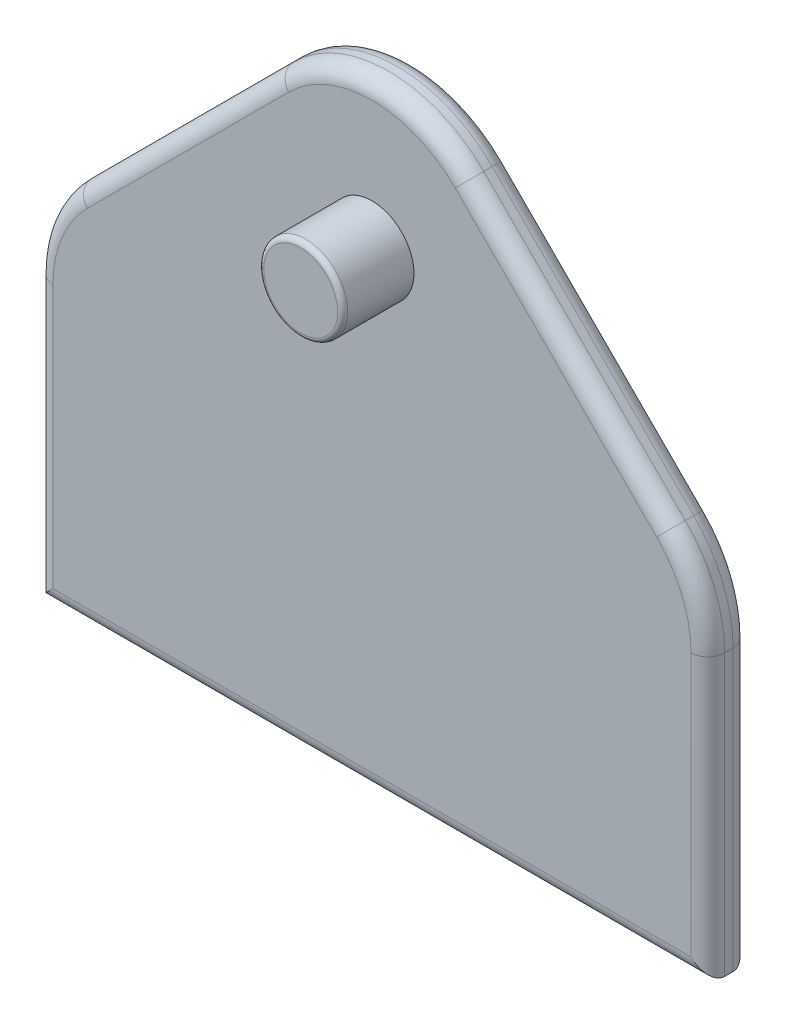
SolidWorks part; units mm, degrees
material "6061-T6 (SS)"
ref_plane "Front Plane" through (0, 0, 0) normal (0, 0, 1) x (1, 0, 0)
ref_plane "Top Plane" through (0, 0, 0) normal (0, 1, 0) x (1, 0, 0)
ref_plane "Right Plane" through (0, 0, 0) normal (1, 0, 0) x (0, 0, -1)
sketch "Sketch1" plane through (0, 0, 0) normal (0, 0, 1) x (1, 0, 0)
  line L0 (-50.8, 0) -> (50.8, 0)
  line L1 (50.8, 0) -> (50.8, 50.8)
  line L2 (50.8, 50.8) -> (0, 101.6)
  line L3 (0, 101.6) -> (-50.8, 50.8)
  line L4 (-50.8, 50.8) -> (-50.8, 0)
  dimension "D1" = 101.6
  dimension "D2" = 50.8
  dimension "D3" = 50.8
  dimension "D4" = 50.8
  dimension "D5" = 101.6
  dimension "D6" = 50.8
  dimension "D7" = 0
extrude "Boss-Extrude1" add sketch "Sketch1" along normal blind 6.35
fillet "Fillet1" radius 2.54 5 edges at (-50.8, 25.4, 6.35) (0, 0, 6.35) (50.8, 25.4, 6.35) (25.4, 76.2, 6.35) (-25.4, 76.2, 6.35)
fillet "Fillet2" radius 2.54 5 edges at (-50.8, 25.4, 0) (0, 0, 0) (50.8, 25.4, 0) (25.4, 76.2, 0) (-25.4, 76.2, 0)
fillet "Fillet3" radius 20.32 9 edges at (50.0561, 50.4918, 5.6061) (50.0561, 50.4918, 0.7439) (-50.0561, 50.4918, 5.6061) (-50.0561, 50.4918, 0.7439) (0, 100.5479, 5.6061) (0, 100.5479, 0.7439) (50.8, 50.8, 3.175) (-50.8, 50.8, 3.175) (0, 101.6, 3.175)
sketch "Sketch3" plane through (0, 0, 6.35) normal (0, 0, 1) x (1, 0, 0)
  line L0 (50.8, 0) -> (-50.8, 0) construction
  circle A0 centre (0, 71.12) radius 6.35
  dimension "D1" = 12.7
  dimension "D2" = 0
  dimension "D3" = 71.12
extrude "Boss-Extrude2" add sketch "Sketch3" along normal mid plane 21.59
fillet "Fillet5" radius 0.762 2 edges at (6.35, 71.12, -4.445) (6.35, 71.12, 17.145)
sketch "Sketch4" plane through (0, 0, 0) normal (0, 0, -1) x (-1, 0, 0)
  line L0 (-38.1, 12.7) -> (38.1, 12.7)
  arc A0 (-38.1, 12.7) -> (38.1, 12.7) centre (0, 12.7) cw
  dimension "D4" = 38.1
  dimension "D1" = 76.2
  dimension "D2" = 0
  dimension "D3" = 12.7
extrude "Boss-Extrude3" add sketch "Sketch4" along normal blind 3.81
